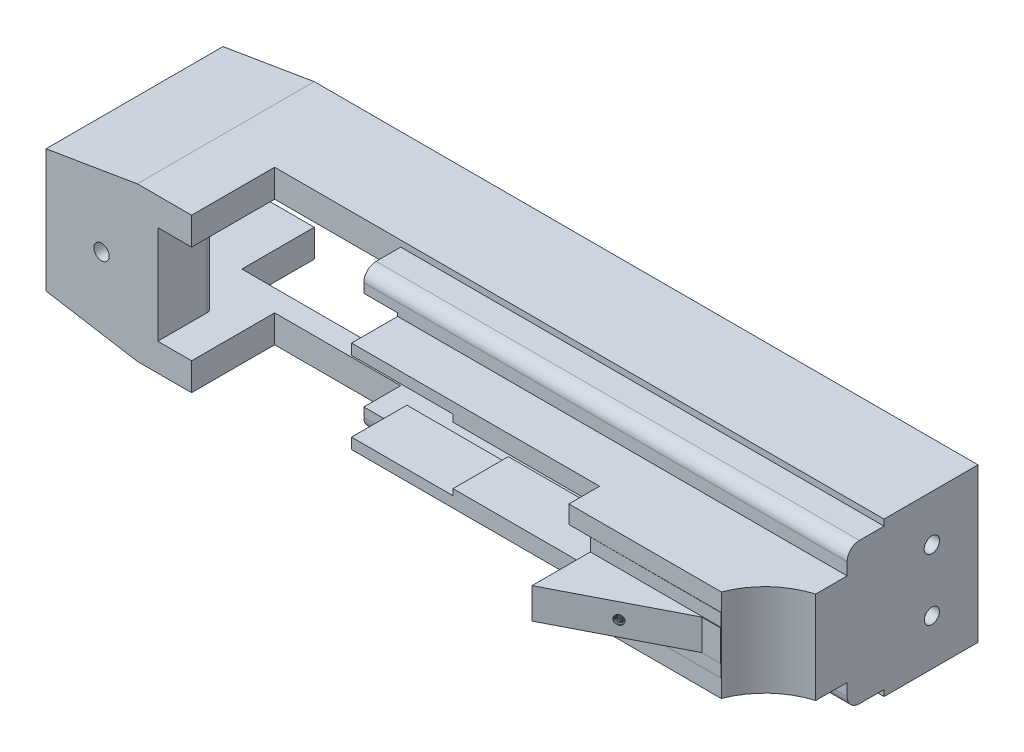
SolidWorks part; units mm, degrees
ref_plane "Front Plane" through (0, 0, 0) normal (0, 0, 1) x (1, 0, 0)
ref_plane "Top Plane" through (0, 0, 0) normal (0, 1, 0) x (1, 0, 0)
ref_plane "Right Plane" through (0, 0, 0) normal (1, 0, 0) x (0, 0, -1)
sketch "Sketch1" plane through (0, 0, 0) normal (0, 0, 1) x (1, 0, 0)
  line L0 (0, 0) -> (245.5, 0)
  line L1 (245.5, 0) -> (245.5, 50)
  line L2 (245.5, 50) -> (0, 50)
  line L3 (0, 50) -> (0, 0)
  dimension "D1" = 245.5
  dimension "D2" = 50
extrude "Boss-Extrude1" add sketch "Sketch1" along normal blind 57.55
sketch "Sketch2" plane through (0, 0, 0) normal (0, 0, -1) x (-1, 0, 0)
  line L0 (0, 9) -> (-205, 9)
  line L1 (0, 50) -> (0, 0) construction
  line L2 (-205, 9) -> (-205, 41)
  line L3 (-205, 41) -> (0, 41)
  line L4 (0, 41) -> (0, 9)
  line L5 (0, 0) -> (-245.5, 0) construction
  line L6 (-245.5, 50) -> (0, 50) construction
  dimension "D1" = 9
  dimension "D2" = 9
  dimension "D3" = 205
extrude "Cut-Extrude1" cut sketch "Sketch2" against normal blind 39.55
sketch "Sketch3" plane through (0, 0, 39.55) normal (0, 0, -1) x (-1, 0, 0)
  line L0 (-10, 9) -> (0, 9)
  line L1 (-205, 9) -> (0, 9) construction
  line L2 (0, 9) -> (0, 41)
  line L3 (0, 41) -> (-10, 41)
  line L4 (0, 41) -> (-205, 41) construction
  line L5 (-10, 41) -> (-10, 9)
  dimension "D1" = 10
extrude "Cut-Extrude2" cut sketch "Sketch3" against normal blind 5
sketch "Sketch4" plane through (0, 0, 39.55) normal (0, 0, -1) x (-1, 0, 0)
  line L0 (0, 9) -> (0, 41) construction
  line L1 (-205, 9) -> (-10, 9) construction
  circle A0 centre (-18.055, 25) radius 2.4875
  dimension "D1" = 4.975
  dimension "D2" = 18.055
  dimension "D3" = 16
extrude "Cut-Extrude3" cut sketch "Sketch4" against normal through all
sketch "Sketch5" plane through (0, 0, 0) normal (0, 0, -1) x (-1, 0, 0)
  line L1 (0, 50) -> (0, 41) construction
  line L4 (0, 45.028) -> (-29.689, 50)
  line L5 (-245.5, 50) -> (0, 50) construction
  line L7 (0, 45.028) -> (0, 51.6223)
  line L8 (0, 51.6223) -> (-29.689, 51.6223)
  line L9 (-29.689, 51.6223) -> (-29.689, 50)
extrude "Cut-Extrude4" cut sketch "Sketch5" against normal through all
sketch "Sketch6" plane through (0, 0, 0) normal (0, 0, -1) x (-1, 0, 0)
  line L1 (0, 9) -> (0, 0) construction
  line L4 (0, 4.972) -> (-29.689, 0)
  line L5 (0, 0) -> (-245.5, 0) construction
  line L7 (-29.689, 0) -> (0.6137, 0)
  line L8 (0.6137, 0) -> (0.6137, 4.972)
  line L9 (0.6137, 4.972) -> (0, 4.972)
extrude "Cut-Extrude5" cut sketch "Sketch6" against normal through all
sketch "Sketch7" plane through (0, 0, 0) normal (0, 0, -1) x (-1, 0, 0)
  line L0 (-29.689, 0) -> (-29.689, 9)
  line L1 (-29.689, 0) -> (-245.5, 0) construction
  line L2 (-205, 9) -> (0, 9) construction
  line L3 (0, 9) -> (0, 4.972) construction
  line L4 (-29.689, 9) -> (-112, 9)
  line L5 (-112, 9) -> (-112, 0)
  line L6 (-112, 0) -> (-29.689, 0)
  point P8 (-112, 4.5)
  dimension "D1" = 29.689
  dimension "D2" = 82.311
extrude "Cut-Extrude6" cut sketch "Sketch7" against normal blind 23.55
sketch "Sketch8" plane through (0, 0, 39.55) normal (0, 0, -1) x (-1, 0, 0)
  line L0 (-37.342, 9) -> (-37.342, 41)
  line L1 (-205, 9) -> (-10, 9) construction
  line L2 (-10, 41) -> (-205, 41) construction
  line L3 (0, 9) -> (0, 41) construction
  line L4 (-37.342, 9) -> (-99.342, 9)
  line L5 (-99.342, 9) -> (-99.342, 41)
  line L6 (-99.342, 41) -> (-37.342, 41)
  dimension "D1" = 37.342
  dimension "D2" = 62
extrude "Cut-Extrude7" cut sketch "Sketch8" against normal through all
sketch "Sketch9" plane through (0, 0, 39.55) normal (0, 0, -1) x (-1, 0, 0)
  line L0 (-99.342, 13.5) -> (-132.342, 13.5)
  line L1 (-99.342, 41) -> (-99.342, 9) construction
  line L2 (-132.342, 13.5) -> (-132.342, 36.5)
  line L3 (-132.342, 36.5) -> (-99.342, 36.5)
  line L4 (-99.342, 36.5) -> (-99.342, 13.5)
  line L5 (-205, 9) -> (-99.342, 9) construction
  line L6 (-99.342, 41) -> (-205, 41) construction
  dimension "D1" = 4.5
  dimension "D2" = 4.5
  dimension "D3" = 33
extrude "Cut-Extrude8" cut sketch "Sketch9" against normal through all
sketch "Sketch10" plane through (0, 0, 39.55) normal (0, 0, -1) x (-1, 0, 0)
  line L0 (-132.342, 34.196) -> (-184.342, 34.196)
  line L1 (-132.342, 36.5) -> (-132.342, 13.5) construction
  line L2 (-184.342, 34.196) -> (-184.342, 15.499)
  line L3 (-184.342, 15.499) -> (-132.342, 15.499)
  line L4 (-132.342, 15.499) -> (-132.342, 34.196)
  line L5 (-205, 9) -> (-99.342, 9) construction
  line L6 (-99.342, 41) -> (-205, 41) construction
  dimension "D1" = 6.499
  dimension "D2" = 6.804
  dimension "D3" = 52
extrude "Cut-Extrude9" cut sketch "Sketch10" against normal through all
sketch "Sketch11" plane through (0, 0, 39.55) normal (0, 0, -1) x (-1, 0, 0)
  line L0 (-184.342, 15.499) -> (-187.342, 15.499)
  line L1 (-187.342, 15.499) -> (-187.342, 34.2927)
  line L2 (-187.342, 34.2927) -> (-184.342, 34.196)
  line L3 (-184.342, 34.196) -> (-184.342, 15.499)
  dimension "D1" = 3
extrude "Cut-Extrude10" cut sketch "Sketch11" against normal blind 3
sketch "Sketch12" plane through (0, 50, 0) normal (0, 1, 0) x (1, 0, 0)
  line L0 (47.342, -57.55) -> (47.342, -30.55)
  line L1 (245.5, -57.55) -> (29.689, -57.55) construction
  line L2 (0, -57.55) -> (0, 0) construction
  line L3 (47.342, -30.55) -> (88.342, -30.55)
  line L4 (88.342, -30.55) -> (88.342, -57.55)
  line L5 (88.342, -57.55) -> (47.342, -57.55)
  point P7 (88.342, -44.05)
  dimension "D1" = 47.342
  dimension "D2" = 41
  dimension "D3" = 27
extrude "Cut-Extrude11" cut sketch "Sketch12" against normal through all
sketch "Sketch13" plane through (0, 50, 0) normal (0, 1, 0) x (1, 0, 0)
  line L0 (88.342, -57.55) -> (88.342, -42.55)
  line L1 (88.342, -57.55) -> (88.342, -30.55) construction
  line L2 (88.342, -42.55) -> (99.342, -42.55)
  line L3 (99.342, -42.55) -> (99.342, -57.55)
  line L4 (245.5, -57.55) -> (88.342, -57.55) construction
  line L5 (99.342, -57.55) -> (88.342, -57.55)
  dimension "D1" = 15
  dimension "D2" = 11
extrude "Cut-Extrude12" cut sketch "Sketch13" against normal through all
sketch "Sketch14" plane through (0, 50, 0) normal (0, 1, 0) x (1, 0, 0)
  line L0 (99.342, -57.55) -> (99.342, -42.55)
  line L1 (99.342, -42.55) -> (245.5, -42.55)
  line L2 (245.5, -57.55) -> (245.5, 0) construction
  line L3 (245.5, -42.55) -> (245.5, -57.55)
  line L4 (245.5, -57.55) -> (99.342, -57.55)
extrude "Cut-Extrude13" cut sketch "Sketch14" against normal blind 10
sketch "Sketch15" plane through (0, 40, 0) normal (0, 1, 0) x (1, 0, 0)
  line L0 (180, -57.55) -> (180, -86.52)
  line L1 (99.342, -57.55) -> (245.5, -57.55) construction
  line L2 (180, -86.52) -> (245.5, -86.52)
  line L3 (245.5, -86.52) -> (245.5, -57.55)
  line L4 (245.5, -57.55) -> (180, -57.55)
  line L5 (0, -57.55) -> (0, 0) construction
  dimension "D1" = 28.97
  dimension "D2" = 180
extrude "Boss-Extrude2" add sketch "Sketch15" against normal blind 30
sketch "Sketch17" plane through (0, 40, 0) normal (0, 1, 0) x (1, 0, 0)
  line L0 (180, -67.55) -> (187, -67.55)
  line L1 (180, -57.55) -> (180, -86.52) construction
  line L2 (99.342, -57.55) -> (180, -57.55) construction
  line L3 (187, -67.55) -> (187, -86.52)
  line L4 (180, -86.52) -> (245.5, -86.52) construction
  line L5 (187, -86.52) -> (180, -86.52)
  line L6 (180, -86.52) -> (180, -67.55)
  dimension "D1" = 10
  dimension "D2" = 7
extrude "Cut-Extrude14" cut sketch "Sketch17" against normal through all
sketch "Sketch18" plane through (0, 0, 57.55) normal (0, 0, -1) x (-1, 0, 0)
  line L0 (-180, 15.499) -> (-184.342, 15.499)
  line L1 (-184.342, 15.499) -> (-184.342, 34.196)
  line L2 (-184.342, 34.196) -> (-180, 34.196)
  line L3 (-180, 34.196) -> (-180, 15.499)
extrude "Cut-Extrude15" cut sketch "Sketch18" against normal through all
sketch "Sketch20" plane through (0, 0, 67.55) normal (0, 0, 1) x (1, 0, 0)
  line L0 (184.342, 34.196) -> (187, 34.196)
  line L1 (187, 10) -> (187, 40) construction
  line L2 (184.342, 34.196) -> (184.342, 15.499)
  line L3 (184.342, 15.499) -> (187, 15.499)
  line L4 (187, 15.499) -> (187, 34.196)
extrude "Cut-Extrude16" cut sketch "Sketch20" against normal blind 18
sketch "Sketch21" plane through (0, 40, 0) normal (0, 1, 0) x (1, 0, 0)
  line L1 (245.5, -86.52) -> (245.5, -42.55) construction
  line L2 (245.5, -67.597) -> (245.5, -86.52)
  line L3 (245.5, -86.52) -> (187, -86.52)
  line L5 (245.5, -67.597) -> (187, -67.55)
  line L7 (187, -67.55) -> (176.1532, -67.55)
  line L8 (176.1532, -67.55) -> (176.1532, -86.52)
  line L9 (176.1532, -86.52) -> (187, -86.52)
  dimension "D1" = 18.923
extrude "Cut-Extrude17" cut sketch "Sketch21" against normal blind 10
sketch "Sketch27" plane through (0, 40, 0) normal (0, 1, 0) x (1, 0, 0)
  line L1 (180, -57.55) -> (180, -67.55) construction
  line L2 (180, -67.519) -> (245.5, -67.519)
  line L3 (245.5, -67.597) -> (245.5, -42.55) construction
  line L4 (187, -67.55) -> (180, -67.55) construction
  line L5 (180, -67.519) -> (180, -67.55)
  line L6 (180, -67.55) -> (245.5, -67.597)
  line L7 (245.5, -67.597) -> (245.5, -67.519)
  dimension "D1" = 0.031
extrude "Cut-Extrude21" cut sketch "Sketch27" against normal blind 5.804
sketch "Sketch22" plane through (0, 10, 0) normal (0, -1, 0) x (1, 0, 0)
  line L0 (187, 67.55) -> (245.5, 67.55)
  line L1 (245.5, 86.52) -> (245.5, 57.55) construction
  line L2 (245.5, 67.55) -> (245.5, 86.52)
  line L3 (245.5, 86.52) -> (187, 86.52)
  line L4 (187, 86.52) -> (187, 67.55)
extrude "Cut-Extrude18" cut sketch "Sketch22" against normal blind 10
sketch "Sketch23" plane through (0, 30, 0) normal (0, 1, 0) x (1, 0, 0)
  line L9 (187, -67.55) -> (187, -86.52) construction
  line L12 (223.471, -67.772) -> (187, -86.52)
  line L13 (223.471, -67.772) -> (245.5, -67.772)
  line L14 (187, -86.52) -> (245.5, -86.52)
  line L15 (245.5, -86.52) -> (245.5, -67.772)
  dimension "D2" = 36.471
extrude "Cut-Extrude20" cut sketch "Sketch23" against normal through all
sketch "Sketch29" plane through (74.2658, 0, 144.4713) normal (0.4572, 0, 0.8894) x (0.8894, 0, -0.4572)
  line L0 (126.7571, 20) -> (126.7571, 30) construction
  line L1 (167.7646, 30) -> (126.7571, 30) construction
  circle A0 centre (147.7571, 24.882) radius 1.5
  dimension "D3" = 3
  dimension "D1" = 21
  dimension "D2" = 5.118
extrude "Cut-Extrude22" cut sketch "Sketch29" against normal blind 8.5
sketch "Sketch31" plane through (0, 0, 0) normal (0, -1, 0) x (1, 0, 0)
  line L0 (88.342, 30.55) -> (245.5, 30.55)
  line L2 (245.5, 57.55) -> (245.5, 0) construction
  line L3 (245.5, 30.55) -> (245.5, 57.55)
  line L4 (245.5, 57.55) -> (99.342, 57.55)
  line L5 (99.342, 57.55) -> (88.342, 57.55)
  line L6 (88.342, 57.55) -> (88.342, 30.55)
extrude "Cut-Extrude23" cut sketch "Sketch31" against normal blind 2
sketch "Sketch32" plane through (0, 2, 0) normal (0, -1, 0) x (1, 0, 0)
  line L0 (99.342, 42.55) -> (245.5, 42.55)
  line L1 (245.5, 30.55) -> (245.5, 57.55) construction
  line L2 (245.5, 42.55) -> (245.5, 57.55)
  line L3 (245.5, 57.55) -> (99.342, 57.55)
  line L4 (99.342, 57.55) -> (99.342, 42.55)
extrude "Cut-Extrude24" cut sketch "Sketch32" against normal blind 8
fillet "Fillet2" radius 4 1 edges at (166.921, 2, 42.55)
sketch "Sketch35" plane through (0, 0, 67.55) normal (0, 0, 1) x (1, 0, 0)
  line L0 (245.5, 20) -> (245.5, 15.797)
  line L1 (245.5, 15.797) -> (187, 15.797)
  line L2 (187, 20) -> (187, 15.499) construction
  line L3 (187, 15.797) -> (187, 20)
  line L4 (187, 20) -> (245.5, 20)
extrude "Boss-Extrude4" add sketch "Sketch35" along normal blind 0.08
sketch "Sketch37" plane through (0, 50, 0) normal (0, 1, 0) x (1, 0, 0)
  line L0 (88.342, -30.55) -> (245.5, -30.55)
  line L1 (245.5, -42.55) -> (245.5, 0) construction
  line L2 (245.5, -30.55) -> (245.5, -42.55)
  line L3 (245.5, -42.55) -> (88.342, -42.55) construction
  line L4 (245.5, -42.55) -> (88.342, -42.55)
  line L5 (88.342, -42.55) -> (88.342, -30.55)
extrude "Cut-Extrude25" cut sketch "Sketch37" against normal blind 2
fillet "Fillet3" radius 4 1 edges at (166.921, 48, 42.55)
sketch "Sketch38" plane through (205, 0, 0) normal (-1, 0, 0) x (0, 0, 1)
  line L0 (30.55, 0) -> (0, 0) construction
  line L1 (30.55, 50) -> (0, 50) construction
  line L2 (0, 41) -> (0, 9) construction
  circle A0 centre (15, 15) radius 2.4445
  circle A1 centre (15, 35) radius 2.5019
  dimension "D1" = 15
  dimension "D2" = 15
  dimension "D3" = 15
  dimension "D4" = 15
extrude "Cut-Extrude26" cut sketch "Sketch38" against normal through all
sketch "Sketch39" plane through (0, 0, 67.772) normal (0, 0, 1) x (1, 0, 0)
  line L0 (229.571, 20) -> (229.571, 30)
  line L1 (223.471, 20) -> (245.5, 20) construction
  line L2 (245.5, 30) -> (223.471, 30) construction
  line L3 (223.471, 20) -> (223.471, 30) construction
  line L4 (229.571, 20) -> (229.571, 12.2217)
  line L6 (253.2973, 12.2217) -> (254.0062, 41.842)
  line L7 (254.0062, 41.842) -> (229.571, 41.842)
  line L8 (229.571, 41.842) -> (229.571, 30)
  line L9 (229.571, 12.2217) -> (229.571, 4.0695)
  line L10 (229.571, 4.0695) -> (253.2973, 4.0695)
  line L11 (253.2973, 4.0695) -> (253.2973, 12.2217)
  dimension "D1" = 6.1
extrude "Cut-Extrude27" cut sketch "Sketch39" against normal blind 15
sketch "Sketch42" plane through (0, 10, 0) normal (0, -1, 0) x (1, 0, 0)
  line L0 (229.571, 67.55) -> (229.571, 52.772)
  line L1 (229.571, 52.772) -> (245.5, 52.772)
  arc A0 (245.5, 52.772) -> (229.571, 67.55) centre (252.4707, 76.2594) cw
  dimension "D1" = 24.5
extrude "Boss-Extrude5" add sketch "Sketch42" against normal blind 30
thread "Thread1" pitch 0.5 method extrude profile "Thread Profile2" start angle 0, offset 0, length 6.5, pitch 0.5, diameter 3
ref_plane "Plane2" through (204.3428, 24.882, 77.6049) normal (0, -1, 0) x (-0.8894, 0, 0.4572)
sketch "Thread Profile2" plane through (204.3428, 24.882, 77.6049) normal (0, -1, 0) x (-0.8894, 0, 0.4572)
  line L0 (0, 0) -> (0, 0.5) construction
  line L11 (0, 0) -> (0, 0.4375)
  line L12 (0, 0.4375) -> (-0.2706, 0.2812)
  line L13 (-0.2706, 0.2812) -> (-0.2706, 0.1562)
  line L15 (-0.2706, 0.1562) -> (0, 0)
  line L17 (-0.2706, 0.2187) -> (0, 0.2187) construction
  point P2 (0, 0)
  dimension "Pitch" = 0.5
  dimension "Profile_Angle" = 60
  dimension "Profile_Land" = 0.125
  dimension "Profile_Height" = 0.2706
fillet "Fillet4" radius 4 1 edges at (10, 25, 39.55)
sketch "Sketch43" plane through (0, 0, 57.55) normal (0, 0, 1) x (1, 0, 0)
  line L0 (37.342, 9) -> (36.342, 9)
  line L1 (37.342, 9) -> (37.342, 41)
  line L2 (37.342, 41) -> (36.342, 41)
  line L3 (36.342, 41) -> (36.342, 9)
  dimension "D1" = 1
extrude "Cut-Extrude28" cut sketch "Sketch43" against normal through all
fillet "Fillet7" radius 2 1 edges at (36.342, 25, 39.55)
sketch "Sketch44" plane through (0, 0, 44.55) normal (0, 0, -1) x (-1, 0, 0)
  line L0 (0, 41) -> (-10, 41)
  line L1 (-10, 41) -> (-10, 9)
  line L2 (-10, 41) -> (-10, 9) construction
  line L3 (-10, 9) -> (0, 9)
  line L4 (0, 9) -> (0, 41)
extrude "Cut-Extrude29" cut sketch "Sketch44" against normal blind 2.85
